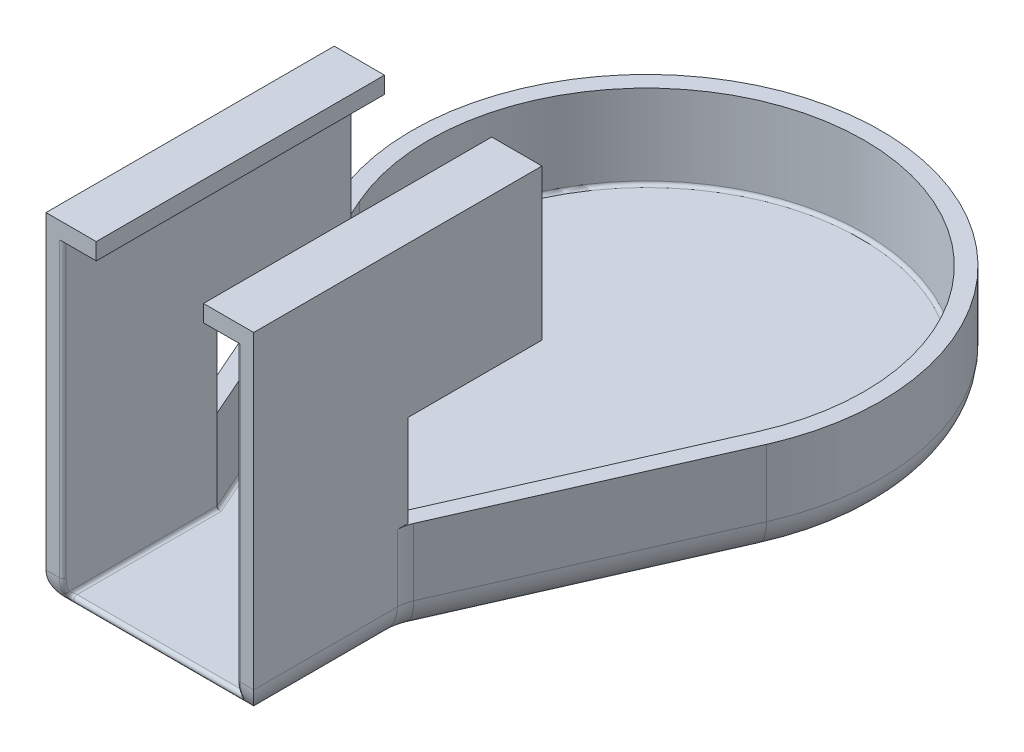
SolidWorks part; units mm, degrees
ref_plane "Front" through (0, 0, 0) normal (0, 0, 1) x (1, 0, 0)
ref_plane "Top" through (0, 0, 0) normal (0, 1, 0) x (1, 0, 0)
ref_plane "Right" through (0, 0, 0) normal (1, 0, 0) x (0, 0, -1)
sketch "Sketch1" plane through (0, 0, 0) normal (0, 1, 0) x (1, 0, 0)
  line L0 (0, 94.7186) -> (0, -179.3984) construction
  line L1 (-64.0548, -28.2309) -> (-31, -103.2309)
  line L2 (-31, -103.2309) -> (-31, -148.2309)
  line L3 (-31, -148.2309) -> (31, -148.2309)
  line L4 (31, -103.2309) -> (31, -148.2309)
  line L5 (64.0548, -28.2309) -> (31, -103.2309)
  arc A0 (64.0548, -28.2309) -> (-64.0548, -28.2309) centre (0, 0) ccw
  point P12 (0, -148.2309)
  dimension "D1" = 70
  dimension "D2" = 120
  dimension "D3" = 31
  dimension "D4" = 45
extrude "Boss-Extrude1" add sketch "Sketch1" along normal blind 30
shell "Shell1" thickness 5 removed face at (0, 15, 148.2309) removed face at (0, 30, 76.8591)
sketch "Sketch2" plane through (0, 30, 0) normal (0, 1, 0) x (1, 0, 0)
  line L1 (-31, -148.2309) -> (-26, -148.2309)
  line L2 (-31, -148.2309) -> (-31, -102.1779)
  line L3 (-31, -102.1779) -> (-26, -102.1779)
  line L4 (-26, -148.2309) -> (-26, -102.1779)
extrude "Boss-Extrude2" add sketch "Sketch2" along normal blind 72.4
sketch "Sketch3" plane through (-26, 0, 0) normal (1, 0, 0) x (0, 0, -1)
  line L0 (-102.1779, 102.4) -> (-102.1779, 30) construction
  line L1 (-148.2309, 102.4) -> (-102.1779, 102.4)
  line L2 (-148.2309, 102.4) -> (-148.2309, 97.4)
  line L3 (-148.2309, 97.4) -> (-102.1779, 97.4)
  line L4 (-102.1779, 102.4) -> (-102.1779, 97.4)
  dimension "D1" = 5
extrude "Boss-Extrude3" add sketch "Sketch3" along normal blind 10
sketch "Sketch4" plane through (0, 0, 102.1779) normal (0, 0, -1) x (-1, 0, 0)
  line L0 (31, 57.4) -> (26, 57.4)
  line L1 (31, 102.4) -> (31, 30) construction
  line L2 (26, 97.4) -> (26, 30) construction
  line L3 (31, 57.4) -> (31, 102.4)
  line L4 (26, 57.4) -> (26, 97.4)
  line L6 (26, 30) -> (31, 30)
  line L7 (31, 30) -> (31, 102.4)
  line L8 (31, 102.4) -> (16, 102.4)
  line L9 (16, 102.4) -> (16, 97.4)
  line L10 (16, 97.4) -> (26, 97.4)
  line L11 (26, 97.4) -> (26, 30)
  line L14 (31, 102.4) -> (16, 102.4)
  line L15 (16, 102.4) -> (16, 97.4)
  line L16 (16, 97.4) -> (26, 97.4)
  dimension "D2" = 40
  dimension "D1" = 0
extrude "Boss-Extrude4" add sketch "Sketch4" along normal blind 40
ref_plane "Plane1" through (0, 0, 0) normal (1, 0, 0) x (0, 0, -1)
mirror "Mirror1" about plane through (0, 0, 0) normal (1, 0, 0) of "Boss-Extrude4", "Boss-Extrude3", "Boss-Extrude2"
fillet "Fillet1" radius 10 8 edges at (-47.5274, 0, 65.7309) (-31, 0, 125.7309) (0, 0, 148.2309) (31, 0, 125.7309) (47.5274, 0, 65.7309) (0, 0, -70) (31, 15, 103.2309) (-31, 15, 103.2309)
fillet "Fillet2" radius 1 10 edges at (26, 53.7, 148.2309) (-26, 53.7, 148.2309) (26, 7.4118, 147.8902) (-26, 7.4118, 147.8902) (-42.7397, 5, 64.1962) (0, 5, -65) (42.7397, 5, 64.1962) (26, 5, 124.5345) (0, 5, 146.8912) (-26, 5, 124.5345)
